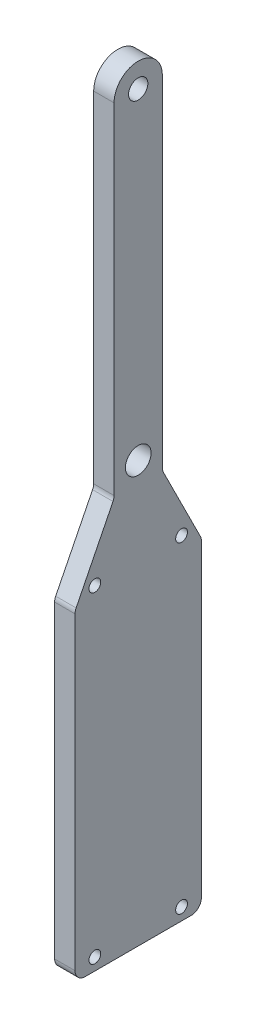
SolidWorks part; units mm, degrees
material "6061 Alloy"
ref_plane "Front Plane" through (0, 0, 0) normal (0, 0, 1) x (1, 0, 0)
ref_plane "Top Plane" through (0, 0, 0) normal (0, 1, 0) x (1, 0, 0)
ref_plane "Right Plane" through (0, 0, 0) normal (1, 0, 0) x (0, 0, -1)
sketch "Sketch1" plane through (0, 0, 0) normal (1, 0, 0) x (0, 0, -1)
  line L0 (-13.4747, 0) -> (13.4747, 0) construction
  line L1 (0, 0) -> (0, 26.9494) construction
  line L2 (-13.4747, 0) -> (0, 26.9494) construction
  line L3 (0, 26.9494) -> (13.4747, 0) construction
  line L4 (13.4747, 0) -> (-13.4747, 0) construction
  line L5 (19.6394, -3.81) -> (-19.6394, -3.81)
  line L6 (-19.6394, -3.81) -> (0, 35.4688)
  line L7 (0, 35.4688) -> (19.6394, -3.81)
  line L8 (0, 26.9494) -> (0, 126.9494) construction
  line L9 (0, 26.9494) -> (0, 126.9494) construction
  line L12 (-7.5, 26.9494) -> (-7.5, 126.9494)
  line L13 (7.5, 26.9494) -> (7.5, 126.9494)
  line L14 (-7.5, 26.9494) -> (-7.5, 20.4688)
  line L15 (7.5, 26.9494) -> (7.5, 20.4688)
  line L16 (-13.4747, 0) -> (13.4747, 0) construction
  line L17 (-13.4747, 0) -> (-13.4747, -100) construction
  line L18 (13.4747, 0) -> (13.4747, -100) construction
  line L19 (-13.4747, -100) -> (13.4747, -100) construction
  line L20 (-19.6394, -3.81) -> (19.6394, -3.81)
  line L21 (-19.6394, -3.81) -> (-19.6394, -103.81)
  line L22 (19.6394, -3.81) -> (19.6394, -103.81)
  line L23 (-19.6394, -103.81) -> (19.6394, -103.81)
  circle A0 centre (-13.4747, 0) radius 1.8288
  circle A1 centre (0, 26.9494) radius 4
  circle A2 centre (13.4747, 0) radius 1.8288
  circle A3 centre (0, 126.9494) radius 3
  arc A6 (-7.5, 26.9494) -> (7.5, 26.9494) centre (0, 26.9494) ccw
  arc A7 (7.5, 126.9494) -> (-7.5, 126.9494) centre (0, 126.9494) ccw
  circle A8 centre (-13.4747, -100) radius 1.8288
  circle A9 centre (13.4747, -100) radius 1.8288
  point P4 (0, 0)
  point P14 (0, 76.9494)
  dimension "D3" = 3.6576
  dimension "D4" = 8
  dimension "D7" = 6
  dimension "D1" = 26.9494
  dimension "D5" = 100
  dimension "D6" = 15
  dimension "D8" = 100
  dimension "D9" = 3.81
  dimension "D2" = 3.81
extrude "Boss-Extrude1" add sketch "Sketch1" along normal blind 6.35 contours A6 L6 L5 L7 A2 A0 | L6 A6 L7 A1 | L13 A7 L12 A6 L6 A1 L7 A3 | A1 L7 L6 | A6 L7 L15 | A6 L14 L6 | A8 | A9 | L20 L21 L23 L22 region at (0, 6.8071, 0) region at (0, 23.0136, -7.1228) region at (0, 23.0136, 7.1228) region at (0, 22.4682, 0) region at (0, 79.7176, 0) region at (0, 32.2331, 0) region at (0, -100, 13.4747) region at (0, -100, -13.4747)
fillet "Fillet1" radius 3.175 6 edges at (3.175, 20.4688, -7.5) (3.175, 20.4688, 7.5) (3.175, -103.81, 19.6394) (3.175, -103.81, -19.6394) (3.175, -3.81, -19.6394) (3.175, -3.81, 19.6394)
